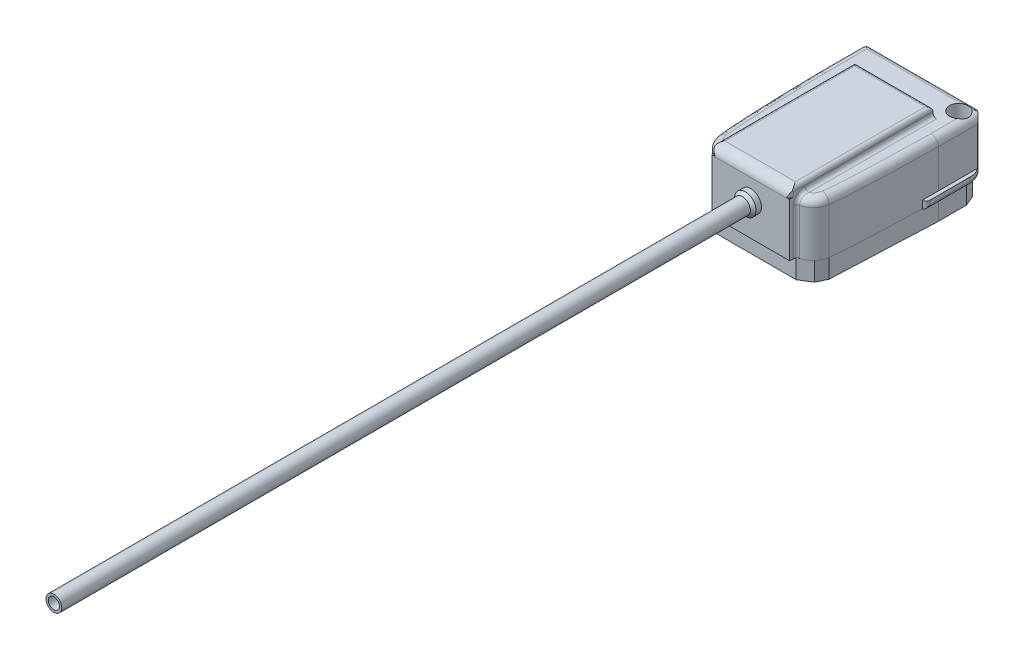
SolidWorks part; units mm, degrees
ref_plane "Front Plane" through (0, 0, 0) normal (0, 0, 1) x (1, 0, 0)
ref_plane "Top Plane" through (0, 0, 0) normal (0, 1, 0) x (1, 0, 0)
ref_plane "Right Plane" through (0, 0, 0) normal (1, 0, 0) x (0, 0, -1)
sketch "Sketch1" plane through (0, 0, 0) normal (0, 0, 1) x (1, 0, 0)
  circle A0 centre (0, 0) radius 4.2
  dimension "D1" = 8.4
extrude "Extrude1" add sketch "Sketch1" along normal blind 366.8
sketch "Sketch2" plane through (0, 0, 0) normal (0, 0, -1) x (-1, 0, 0)
  circle A0 centre (0, 0) radius 5.7
  dimension "D1" = 11.4
extrude "Extrude2" add sketch "Sketch2" along normal blind 4.4
chamfer "Chamfer1" distance 1.5 angle 45 1 edges at (-5.7, 0, 0)
sketch "Sketch3" plane through (0, 0, -4.4) normal (0, 0, -1) x (-1, 0, 0)
  line L1 (-34.1, 15.75) -> (34.1, 15.75)
  line L2 (-34.1, 15.75) -> (-34.1, -17.25)
  line L3 (-34.1, -17.25) -> (34.1, -17.25)
  line L4 (34.1, 15.75) -> (34.1, -17.25)
  circle A0 centre (0, 0) radius 5.7 construction
  dimension "D4" = 17.25
  dimension "D1" = 33
  dimension "D2" = 68.2
  dimension "D3" = 34.1
extrude "Extrude3" add sketch "Sketch3" along normal blind 92.8
sketch "Sketch4" plane through (-34.1, 0, 0) normal (-1, 0, 0) x (0, 0, 1)
  line L0 (-97.2, 15.75) -> (-4.4, 15.75) construction
  line L1 (-80.6, 41.999) -> (-107.8441, 41.999)
  line L2 (-80.6, 41.999) -> (-80.6, 11.15)
  line L3 (-80.6, 11.15) -> (-107.8441, 11.15)
  line L4 (-107.8441, 41.999) -> (-107.8441, 11.15)
  line L5 (-97.2, -17.25) -> (-97.2, 15.75) construction
  dimension "D1" = 4.6
  dimension "D2" = 16.6
extrude "Extrude4" cut sketch "Sketch4" against normal up to next
sketch "Sketch5" plane through (0, 0, -80.6) normal (0, 0, -1) x (-1, 0, 0)
  line L1 (20.75, 22.4945) -> (34.1, 22.4945)
  line L2 (20.75, 22.4945) -> (20.75, 11.15)
  line L3 (20.75, 11.15) -> (34.1, 11.15)
  line L4 (34.1, 22.4945) -> (34.1, 11.15)
  line L5 (-20.75, 22.4945) -> (-34.1, 22.4945)
  line L6 (-20.75, 22.4945) -> (-20.75, 11.15)
  line L7 (-20.75, 11.15) -> (-34.1, 11.15)
  line L8 (-34.1, 22.4945) -> (-34.1, 11.15)
  dimension "D1" = 41.5
  dimension "D2" = 13.35
  dimension "D3" = 13.35
extrude "Extrude5" cut sketch "Sketch5" against normal through all
sketch "Sketch6" plane through (0, 0, -97.2) normal (0, 0, -1) x (-1, 0, 0)
  line L0 (-34.1, -17.25) -> (34.1, -17.25) construction
  line L1 (32.1, 16.9028) -> (44.4445, 16.9028)
  line L2 (32.1, 16.9028) -> (32.1, -13.25)
  line L3 (32.1, -13.25) -> (44.4445, -13.25)
  line L4 (44.4445, 16.9028) -> (44.4445, -13.25)
  line L5 (-32.1, 22.2797) -> (-36.4812, 22.2797)
  line L6 (-32.1, 22.2797) -> (-32.1, -13.25)
  line L7 (-32.1, -13.25) -> (-36.4812, -13.25)
  line L8 (-36.4812, 22.2797) -> (-36.4812, -13.25)
  line L9 (-34.1, 11.15) -> (-34.1, -17.25) construction
  line L10 (34.1, -17.25) -> (34.1, 11.15) construction
  dimension "D1" = 4
  dimension "D2" = 4
  dimension "D3" = 2
  dimension "D4" = 2
extrude "Extrude6" cut sketch "Sketch6" against normal through all
sketch "Sketch7" plane through (0, -13.25, 0) normal (0, 1, 0) x (1, 0, 0)
  line L0 (32.1, 4.4) -> (32.1, 97.2) construction
  line L1 (58.6671, 1.609) -> (32.1, 1.609)
  line L2 (58.6671, 1.609) -> (58.6671, 63.7)
  line L3 (58.6671, 63.7) -> (32.1, 63.7)
  line L4 (32.1, 1.609) -> (32.1, 63.7)
  line L5 (-32.1, 4.4) -> (-32.1, 97.2) construction
  line L6 (-32.1, 63.7) -> (-46.2188, 63.7)
  line L7 (-32.1, 63.7) -> (-32.1, -25.5687)
  line L8 (-32.1, -25.5687) -> (-46.2188, -25.5687)
  line L9 (-46.2188, 63.7) -> (-46.2188, -25.5687)
  line L10 (-32.1, 97.2) -> (-34.1, 97.2) construction
  line L11 (34.1, 97.2) -> (32.1, 97.2) construction
  dimension "D1" = 33.5
  dimension "D2" = 33.5
extrude "Extrude7" cut sketch "Sketch7" against normal through all
fillet "Fillet2" radius 3 1 edges at (0, 11.15, -97.2)
fillet "Fillet3" radius 10 2 edges at (34.1, -15.25, -97.2) (-34.1, -15.25, -97.2)
fillet "Fillet20" radius 2 5 edges at (20.75, 13.45, -4.4) (20.75, 15.75, -42.5) (0, 15.75, -80.6) (-20.75, 15.75, -42.5) (-20.75, 13.45, -4.4)
fillet "Fillet7" radius 2 7 edges at (31.1711, -17.25, -94.2711) (-31.1711, -17.25, -94.2711) (-34.1, -15.25, -63.7) (34.1, -15.25, -63.7) (34.1, -17.25, -75.45) (0, -17.25, -97.2) (-34.1, -17.25, -75.45)
sketch "Sketch10" plane through (0, 15.75, 0) normal (0, 1, 0) x (1, 0, 0)
  line L0 (32.1, 4.4) -> (32.1, 93.2) construction
  line L2 (48.4518, 2.5489) -> (32.1, 35.6175)
  line L3 (-24.1, 97.2) -> (24.1, 97.2) construction
  line L4 (32.1, 35.6175) -> (32.1, 72.2)
  line L5 (48.4518, 2.5489) -> (34.583, 0.9729)
  line L6 (34.583, 0.9729) -> (26.1, 4.4)
  line L7 (-26.1, 4.4) -> (-37.3372, -2.8116)
  line L8 (-37.3372, -2.8116) -> (-32.1, 42.0539)
  line L9 (-32.1, 93.2) -> (-32.1, 4.4) construction
  line L10 (-32.1, 42.0539) -> (-32.1, 72.2)
  line L11 (18.75, 4.4) -> (18.75, 78.6) construction
  line L12 (-18.75, 4.4) -> (18.75, 4.4) construction
  spline S0 degree 3 poles (32.1, 72.2) (31.9027, 62.1371) (31.5864, 46.0005) (30.5599, 25.0431) (29.4595, 12.1255) (26.788, 5.9822) (26.1, 4.4) knots 0 0 0 0 0.440913 0.707031 0.924545 1 1 1 1
  spline S1 degree 3 poles (-32.1, 72.2) (-31.9027, 62.1371) (-31.5864, 46.0005) (-30.5599, 25.0431) (-29.4595, 12.1255) (-26.788, 5.9822) (-26.1, 4.4) knots 0 0 0 0 0.440913 0.707031 0.924545 1 1 1 1
  dimension "D1" = 25
  dimension "D2" = 6
extrude "Extrude10" cut sketch "Sketch10" against normal through all
sketch "Sketch11" plane through (0, 11.15, 0) normal (0, 1, 0) x (1, 0, 0)
  line L0 (20.75, 4.4) -> (20.75, 80.6) construction
  line L1 (20.75, 7.9) -> (51.0117, 7.9)
  line L2 (20.75, 7.9) -> (20.75, -9.7349)
  line L3 (20.75, -9.7349) -> (51.0117, -9.7349)
  line L4 (51.0117, 7.9) -> (51.0117, -9.7349)
  line L5 (-20.75, 6.4) -> (-20.75, 80.6) construction
  line L6 (-20.75, 7.9) -> (-46.0804, 7.9)
  line L7 (-20.75, 7.9) -> (-20.75, -17.0396)
  line L8 (-20.75, -17.0396) -> (-46.0804, -17.0396)
  line L9 (-46.0804, 7.9) -> (-46.0804, -17.0396)
  line L10 (-18.75, 4.4) -> (18.75, 4.4) construction
  dimension "D1" = 3.5
  dimension "D2" = 3.5
extrude "Extrude11" cut sketch "Sketch11" against normal through all
fillet "Fillet9" radius 10 2 edges at (27.5599, -3.05, -7.9) (-27.5599, -3.05, -7.9)
fillet "Fillet22" radius 4 6 edges at (26.6935, 11.15, -10.636) (32.1, 11.15, -82.7) (-32.1, 11.15, -82.7) (-26.6935, 11.15, -10.636)
fillet "Fillet13" radius 2 6 edges at (-20.75, -5.05, -7.9) (20.75, -5.05, -7.9) (20.75, 11.15, -46.2662) (20.75, 9.6387, -8.7731) (-20.75, 11.15, -46.2662) (-20.75, 10.1521, -9.2642)
sketch "Sketch14" plane through (20.75, 0, 0) normal (1, 0, 0) x (0, 0, -1)
  line L4 (9.4, 15.75) -> (9.4, 23.6066)
  line L5 (9.4, 23.6066) -> (-2.6621, 20.3015)
  line L6 (-2.6621, 20.3015) -> (2.008, 10.2427)
  line L7 (2.008, 10.2427) -> (4.4, 10.75)
  arc A0 (9.4, 15.75) -> (4.4, 10.75) centre (9.4, 10.75) ccw
  dimension "D3" = 10
extrude "Extrude12" cut sketch "Sketch14" against normal through all
sketch "Sketch15" plane through (0, 11.15, 0) normal (0, 1, 0) x (1, 0, 0)
  line L0 (-24.1, 97.2) -> (24.1, 97.2) construction
  line L1 (32.1, 72.2) -> (32.1, 93.2) construction
  circle A0 centre (25.1, 90.2) radius 5
  dimension "D1" = 10
  dimension "D2" = 7
  dimension "D3" = 7
extrude "Extrude13" cut sketch "Sketch15" against normal blind 10
sketch "Sketch16" plane through (0, 1.15, 0) normal (0, 1, 0) x (1, 0, 0)
  circle A0 centre (25.1, 90.2) radius 2.5
  dimension "D1" = 5
extrude "Extrude14" cut sketch "Sketch16" against normal blind 10
sketch "Sketch17" plane through (0, -17.25, 0) normal (0, -1, 0) x (1, 0, 0)
  line L0 (24.1, -97.2) -> (-24.1, -97.2) construction
  line L1 (32.1, -87.2) -> (32.1, -72.2) construction
  line L2 (-32.1, -72.2) -> (-32.1, -87.2) construction
  line L4 (-19.9, -35.4) -> (-11.9, -35.4)
  line L5 (-19.9, -35.4) -> (-19.9, -43.4)
  line L6 (-19.9, -43.4) -> (-11.9, -43.4)
  line L7 (-11.9, -35.4) -> (-11.9, -43.4)
  line L8 (11.9, -35.4) -> (19.9, -35.4)
  line L9 (11.9, -35.4) -> (11.9, -43.4)
  line L10 (11.9, -43.4) -> (19.9, -43.4)
  line L11 (19.9, -35.4) -> (19.9, -43.4)
  line L12 (11.9, -67.2) -> (19.9, -67.2)
  line L13 (11.9, -67.2) -> (11.9, -75.2)
  line L14 (11.9, -75.2) -> (19.9, -75.2)
  line L15 (19.9, -67.2) -> (19.9, -75.2)
  line L16 (-19.9, -67.2) -> (-11.9, -67.2)
  line L17 (-19.9, -67.2) -> (-19.9, -75.2)
  line L18 (-19.9, -75.2) -> (-11.9, -75.2)
  line L19 (-11.9, -67.2) -> (-11.9, -75.2)
  circle A0 centre (-15.9, -39.4) radius 7.5
  circle A1 centre (15.9, -39.4) radius 7.5
  circle A2 centre (-15.9, -71.2) radius 7.5
  circle A3 centre (15.9, -71.2) radius 7.5
  dimension "D1" = 15
  dimension "D2" = 15
  dimension "D3" = 15
  dimension "D4" = 15
  dimension "D26" = 8
  dimension "D5" = 31.8
  dimension "D6" = 31.8
  dimension "D7" = 26
  dimension "D8" = 26
  dimension "D9" = 16.2
  dimension "D10" = 31.8
  dimension "D11" = 31.8
  dimension "D12" = 16.2
  dimension "D13" = 16.2
  dimension "D14" = 4
  dimension "D15" = 4
  dimension "D16" = 4
  dimension "D17" = 4
  dimension "D18" = 8
  dimension "D19" = 8
  dimension "D20" = 4
  dimension "D21" = 4
  dimension "D22" = 8
  dimension "D23" = 8
  dimension "D24" = 4
  dimension "D25" = 4
  dimension "D27" = 8
  dimension "D28" = 4
  dimension "D29" = 4
extrude "Extrude15" cut sketch "Sketch17" against normal blind 3
sketch "Sketch18" plane through (0, -17.25, 0) normal (0, -1, 0) x (1, 0, 0)
  line L0 (-27.224, -11.1854) -> (-21.1699, -7.4538)
  line L1 (-27.224, -11.1854) -> (-29.6731, -16.4611)
  line L2 (-29.6731, -16.4611) -> (-32.1, -72.2)
  line L3 (-32.1, -72.2) -> (-32.1, -87.2)
  line L4 (-32.1, -87.2) -> (-29.7569, -92.8569)
  line L5 (-29.7569, -92.8569) -> (-24.1, -95.2)
  line L6 (-24.1, -95.2) -> (24.1, -95.2)
  line L7 (24.1, -95.2) -> (29.7569, -92.8569)
  line L8 (29.7569, -92.8569) -> (32.1, -87.2)
  line L9 (32.1, -87.2) -> (32.1, -72.2)
  line L10 (32.1, -72.2) -> (29.6731, -16.4611)
  line L11 (29.6731, -16.4611) -> (27.224, -11.1854)
  line L12 (27.224, -11.1854) -> (21.1699, -7.4538)
  line L13 (21.1699, -7.4538) -> (-21.1699, -7.4538)
  arc A0 (-22.2534, -8.1651) -> (-20.75, -6.2277) centre (-22.75, -6.2277) ccw construction
  arc A1 (-22.2534, -8.1651) -> (-29.6731, -16.4611) centre (-19.7703, -17.8519) ccw construction
  arc A2 (-32.1, -87.2) -> (-24.1, -95.2) centre (-24.1, -87.2) ccw construction
  arc A3 (24.1, -95.2) -> (32.1, -87.2) centre (24.1, -87.2) ccw construction
  arc A4 (29.6731, -16.4611) -> (22.2534, -8.1651) centre (19.7703, -17.8519) ccw construction
  arc A5 (20.75, -6.2277) -> (22.2534, -8.1651) centre (22.75, -6.2277) ccw construction
  circle A6 centre (-15.9, -39.4) radius 7.5
  circle A7 centre (15.9, -39.4) radius 7.5
  circle A8 centre (15.9, -71.2) radius 7.5
  circle A9 centre (-15.9, -71.2) radius 7.5
extrude "Extrude16" add sketch "Sketch18" along normal blind 10.05
sketch "Sketch19" plane through (0, -17.25, 0) normal (0, -1, 0) x (1, 0, 0)
  line L1 (-19.9, -35.4) -> (-11.9, -35.4)
  line L2 (-19.9, -35.4) -> (-19.9, -43.4)
  line L3 (-19.9, -43.4) -> (-11.9, -43.4)
  line L4 (-11.9, -35.4) -> (-11.9, -43.4)
  line L5 (11.9, -35.4) -> (19.9, -35.4)
  line L6 (11.9, -35.4) -> (11.9, -43.4)
  line L7 (11.9, -43.4) -> (19.9, -43.4)
  line L8 (19.9, -35.4) -> (19.9, -43.4)
  line L9 (11.9, -67.2) -> (19.9, -67.2)
  line L10 (11.9, -67.2) -> (11.9, -75.2)
  line L11 (11.9, -75.2) -> (19.9, -75.2)
  line L12 (19.9, -67.2) -> (19.9, -75.2)
  line L13 (-19.9, -67.2) -> (-11.9, -67.2)
  line L14 (-19.9, -67.2) -> (-19.9, -75.2)
  line L15 (-19.9, -75.2) -> (-11.9, -75.2)
  line L16 (-11.9, -67.2) -> (-11.9, -75.2)
extrude "Extrude17" add sketch "Sketch19" along normal blind 10.05
ref_plane "Plane1" through (0, 0, 376.8) normal (0, 0, 1) x (1, 0, 0)
sketch "Sketch21" plane through (0, 0, 376.8) normal (0, 0, 1) x (1, 0, 0)
  circle A0 centre (0, 0) radius 3
  dimension "D1" = 6
extrude "Cut-Extrude2" cut sketch "Sketch21" along direction (0, 0, -1) on the side against the normal up to surface (381.2 mm away) up to face at (0, -3.25, -4.4)
